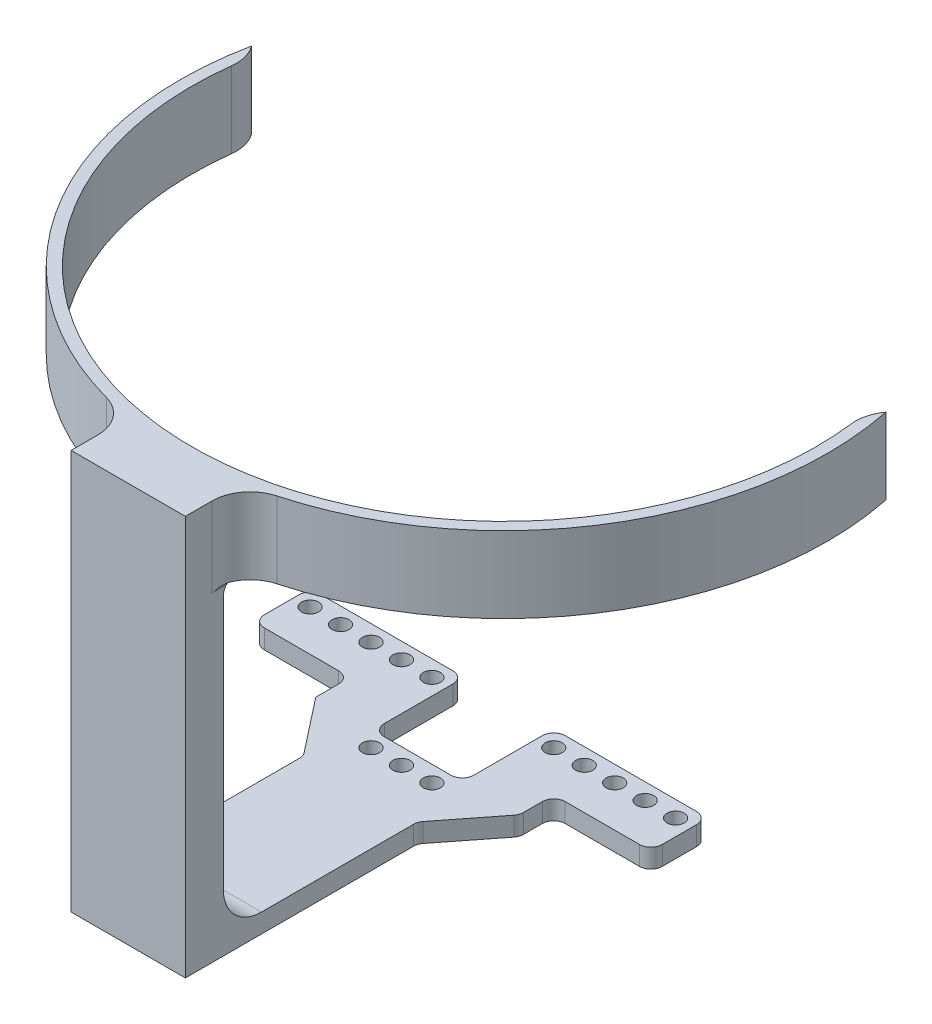
SolidWorks part; units mm, degrees
ref_plane "前视基准面" through (0, 0, 0) normal (0, 0, 1) x (1, 0, 0)
ref_plane "上视基准面" through (0, 0, 0) normal (0, 1, 0) x (1, 0, 0)
ref_plane "右视基准面" through (0, 0, 0) normal (1, 0, 0) x (0, 0, -1)
sketch "草图2" plane through (0, 0, 0) normal (0, 1, 0) x (1, 0, 0)
  line L0 (-48, 45.75) -> (-40, 45.75) construction
  line L1 (-52.25, 50) -> (52.25, 50)
  line L2 (-52.25, 50) -> (-52.25, 35)
  line L4 (52.25, 50) -> (52.25, 35)
  line L5 (-52.25, 50) -> (52.25, -50) construction
  line L6 (-52.25, -50) -> (52.25, 50) construction
  line L7 (0, 50) -> (0, -50) construction
  line L8 (-26.75, 35) -> (-52.25, 35)
  line L9 (-11.75, 26) -> (11.75, 26)
  line L10 (-11.75, 26) -> (-11.75, 50)
  line L11 (-11.75, 50) -> (11.75, 50)
  line L12 (11.75, 26) -> (11.75, 50)
  line L13 (-11.75, 26) -> (11.75, 50) construction
  line L14 (-11.75, 50) -> (11.75, 26) construction
  line L15 (-26.75, 35) -> (-26.75, 26)
  line L17 (26.75, 35) -> (52.25, 35)
  line L21 (-52.25, 35) -> (-52.25, -50) construction
  line L23 (-52.25, -50) -> (52.25, -50) construction
  line L25 (52.25, 35) -> (52.25, -50) construction
  line L27 (-26.75, 26) -> (-26.75, 11) construction
  line L29 (26.75, 35) -> (26.75, 26)
  line L34 (-26.75, 26) -> (-15, 11)
  line L35 (11.495, 11) -> (15, 11) construction
  line L36 (-15, 11) -> (-15, -50)
  line L37 (-15, -50) -> (15, -50)
  line L38 (15, 11) -> (15, -50)
  line L39 (26.75, 26) -> (15, 11)
  line L40 (-15, 11) -> (-11.495, 11) construction
  line L41 (-11.495, 11) -> (0, 11) construction
  line L42 (0, 11) -> (11.495, 11) construction
  circle A0 centre (-48, 45.75) radius 2.25
  circle A1 centre (-40, 45.75) radius 2.25
  circle A2 centre (-32, 45.75) radius 2.25
  circle A3 centre (-24, 45.75) radius 2.25
  circle A4 centre (-16, 45.75) radius 2.25
  circle A5 centre (48, 45.75) radius 2.25
  circle A6 centre (40, 45.75) radius 2.25
  circle A7 centre (32, 45.75) radius 2.25
  circle A8 centre (24, 45.75) radius 2.25
  circle A9 centre (16, 45.75) radius 2.25
  circle A10 centre (-8, 21.75) radius 2.25
  circle A11 centre (0, 21.75) radius 2.25
  circle A13 centre (8, 21.75) radius 2.25
  point P0 (0, 0)
  point P20 (0, 38)
  point P55 (0, -50)
  dimension "D3" = 4.5
  dimension "D4" = 4.25
  dimension "D10" = 4.5
  dimension "D11" = 24
  dimension "D12" = 4.5
  dimension "D13" = 8
  dimension "D1" = 104.5
  dimension "D2" = 100
  dimension "D5" = 4.25
  dimension "D7" = 8
  dimension "D8" = 4.25
  dimension "D9" = 4.25
  dimension "D14" = 15
  dimension "D15" = 15
  dimension "D16" = 15
  dimension "D17" = 30
  dimension "D18" = 15
  dimension "D6" = 5
extrude "凸台-拉伸1" add sketch "草图2" along normal blind 5 contours L12 L9 L10 L1 L2 L4 A8 A6 A0 A1 A2 A3 A4 A5 A7 A9 region at (0, 0, -7.4708)
sketch "草图3" plane through (0, 5, 0) normal (0, 1, 0) x (1, 0, 0)
  line L0 (-15, 11) -> (-15, -50) construction
  line L1 (-15, -40) -> (15, -40)
  line L2 (-15, -40) -> (-15, -50)
  line L3 (-15, -50) -> (15, -50)
  line L4 (15, -40) -> (15, -50)
  line L5 (-15, -40) -> (15, -50) construction
  line L6 (-15, -50) -> (15, -40) construction
  point P0 (0, -45)
  point P8 (0, 0)
  point P9 (0, 0)
  point P10 (0, -9.9223)
  dimension "D1" = 10
extrude "凸台-拉伸2" add sketch "草图3" along normal blind 80
sketch "草图6" plane through (0, 85, 0) normal (0, 1, 0) x (1, 0, 0)
  line L0 (-15, -35) -> (-15, -50)
  line L1 (-15, 11) -> (-15, -40) construction
  line L2 (-15, -50) -> (15, -50)
  line L3 (15, -50) -> (15, -35)
  line L4 (15, 11) -> (15, -40) construction
  line L5 (-83.2827, 65.666) -> (-80.2185, 65.666)
  line L6 (80.2185, 65.666) -> (83.2827, 65.666)
  arc A0 (-83.2827, 65.666) -> (-15, -35) centre (0, 48.666) ccw
  arc A1 (-80.2185, 65.666) -> (80.2185, 65.666) centre (0, 48.666) ccw
  arc A2 (15, -35) -> (83.2827, 65.666) centre (0, 48.666) ccw
  dimension "D1" = 170
  dimension "D2" = 3
  dimension "D3" = 15
  dimension "D4" = 17
extrude "凸台-拉伸3" add sketch "草图6" along normal blind 20
fillet "圆角1" radius 10 5 edges at (0, 5, 40) (-15, 95, 35) (15, 95, 35) (80.2185, 95, -65.666) (-80.2185, 95, -65.666)
fillet "圆角2" radius 3 14 edges at (52.25, 2.5, -50) (52.25, 2.5, -35) (26.75, 2.5, -35) (26.75, 2.5, -26) (15, 2.5, -11) (-15, 2.5, -11) (-26.75, 2.5, -35) (-52.25, 2.5, -35) (-52.25, 2.5, -50) (-11.75, 2.5, -50) (-11.75, 2.5, -26) (11.75, 2.5, -26) (11.75, 2.5, -50) (0, 85, 40)
fillet "圆角3" radius 1 2 edges at (-15, 85, 39.9928) (15, 85, 39.9928)
